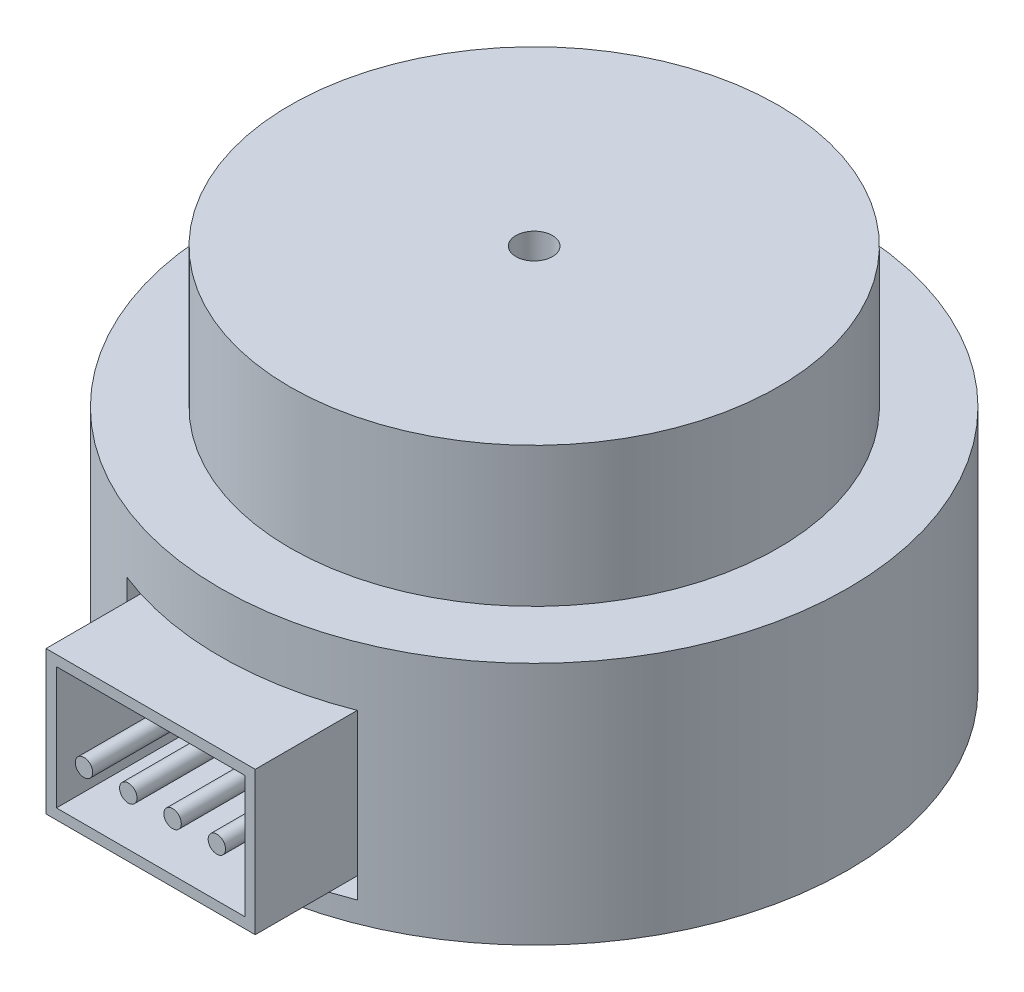
SolidWorks part; units mm, degrees
ref_plane "Plan de face" through (0, 0, 0) normal (0, 0, 1) x (1, 0, 0)
ref_plane "Plan de dessus" through (0, 0, 0) normal (0, 1, 0) x (1, 0, 0)
ref_plane "Plan de droite" through (0, 0, 0) normal (1, 0, 0) x (0, 0, -1)
sketch "Esquisse1" plane through (0, 0, 0) normal (0, 0, 1) x (1, 0, 0)
  line L0 (0, 0) -> (0, 24.7971) construction
  line L1 (-4.5, 0) -> (-9, 0)
  line L2 (-0.525, 3) -> (-0.525, 11)
  line L3 (-7, 7) -> (-9, 7)
  line L4 (-9, 0) -> (-9, 7)
  line L6 (-7, 7) -> (-7, 11)
  line L7 (-7, 11) -> (-0.525, 11)
  line L9 (-0.525, 3) -> (-4.5, 3)
  line L10 (-4.5, 0) -> (-4.5, 3)
  dimension "D1" = 1.05
  dimension "D2" = 4.5
  dimension "D3" = 7
  dimension "D4" = 9
  dimension "D5" = 11
  dimension "D6" = 3
  dimension "D7" = 4
revolve "Révolution1" add sketch "Esquisse1" angle 360 about L0
ref_plane "Plan1" through (0, 0, 9) normal (0, 0, 1) x (1, 0, 0)
sketch "Esquisse2" plane through (0, 0, 9) normal (0, 0, 1) x (1, 0, 0)
  line L1 (-3, 5.0049) -> (3, 5.0049)
  line L2 (-3, 5.0049) -> (-3, 0.8953)
  line L3 (-3, 0.8953) -> (3, 0.8953)
  line L4 (3, 5.0049) -> (3, 0.8953)
  dimension "D1" = 6
  dimension "D2" = 3
extrude "Boss.-Extru.1" add sketch "Esquisse2" along normal blind 2 and the other way blind 0.5288
sketch "Esquisse3" plane through (0, 0, 9) normal (0, 0, 1) x (1, 0, 0)
  line L0 (-2.7, 2.5953) -> (2.7, 2.5953) construction
  line L1 (-3, 5.0049) -> (3, 5.0049)
  line L2 (-3, 5.0049) -> (-3, 0.8953)
  line L3 (-3, 0.8953) -> (3, 0.8953)
  line L4 (3, 5.0049) -> (3, 0.8953)
  line L5 (-3.3, 5.3049) -> (3.3, 5.3049)
  line L6 (-3.3, 5.3049) -> (-3.3, 0.5953)
  line L7 (-3.3, 0.5953) -> (3.3, 0.5953)
  line L8 (3.3, 5.3049) -> (3.3, 0.5953)
  line L9 (-2.7, 4.7049) -> (2.7, 4.7049)
  line L10 (-2.7, 4.7049) -> (-2.7, 1.1953)
  line L11 (-2.7, 1.1953) -> (2.7, 1.1953)
  line L12 (2.7, 4.7049) -> (2.7, 1.1953)
  circle A0 centre (-1.9101, 2.5953) radius 0.25
  circle A1 centre (-0.6401, 2.5953) radius 0.25
  circle A2 centre (0.6299, 2.5953) radius 0.25
  circle A3 centre (1.9, 2.5953) radius 0.25
  dimension "D10" = 0.5
  dimension "D11" = 0.5
  dimension "D12" = 0.5
  dimension "D13" = 0.5
  dimension "D1" = 0.3
  dimension "D2" = 0.3
  dimension "D3" = 0.3
  dimension "D4" = 0.3
  dimension "D5" = 0.3
  dimension "D6" = 0.3
  dimension "D7" = 0.3
  dimension "D8" = 0.3
  dimension "D9" = 1.4
  dimension "D14" = 1.27
  dimension "D15" = 1.27
  dimension "D16" = 1.2701
  dimension "D17" = 0.8
extrude "Enlèv. mat.-Extru.1" cut sketch "Esquisse3" against normal blind 2 and the other way blind 2 contours L8 L5 L6 L7 L1 L4 L3 L2 | L10 L0 A0 A1 A2 A3 L12 L9 | L0 L10 L11 L12 A3 A2 A1 A0 region at (0.0002, 3.684, 9) region at (0.0003, 1.8628, 9) region at (0, 5.2238, 9)
